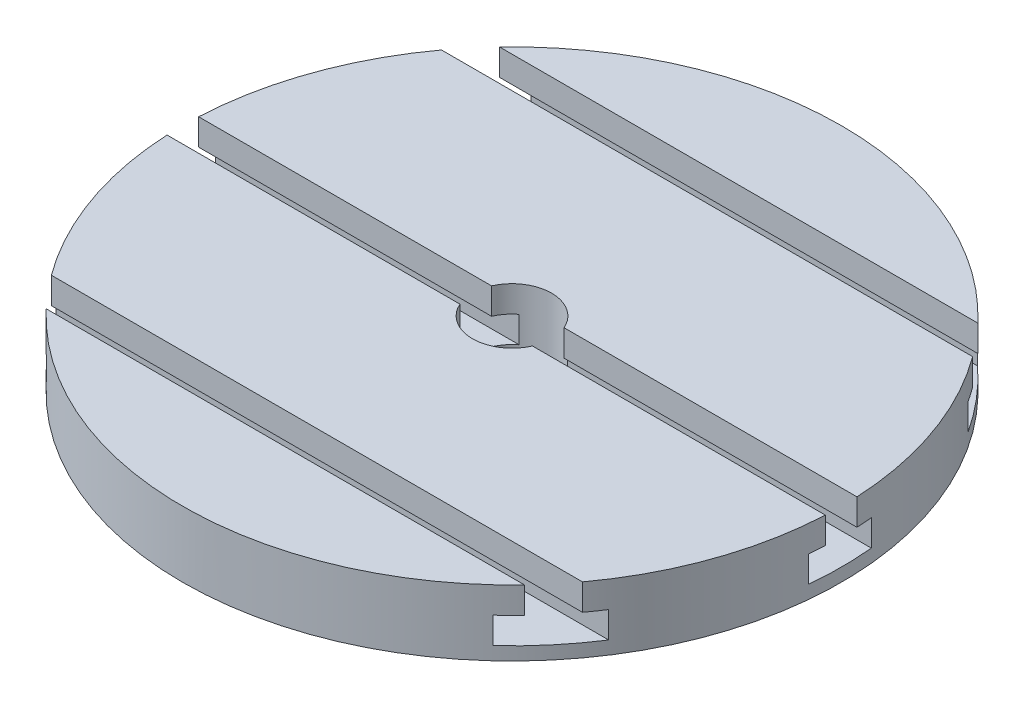
SolidWorks part; units mm, degrees
ref_plane "Спереди" through (0, 0, 0) normal (0, 0, 1) x (1, 0, 0)
ref_plane "Сверху" through (0, 0, 0) normal (0, 1, 0) x (1, 0, 0)
ref_plane "Справа" through (0, 0, 0) normal (1, 0, 0) x (0, 0, -1)
sketch "Эскиз1" plane through (0, 0, 0) normal (1, 0, 0) x (0, 0, -1)
  line L0 (0, -12.6281) -> (0, 29.9138) construction
  line L1 (15, 0) -> (125, 0)
  line L2 (15, 0) -> (15, 25)
  line L3 (15, 25) -> (125, 25)
  line L4 (125, 0) -> (125, 25)
revolve "Повернуть1" add sketch "Эскиз1" angle 360 about L0
sketch "Эскиз2" plane through (0, 0, 0) normal (1, 0, 0) x (0, 0, -1)
  line L1 (11.8734, 5) -> (11.8734, 15)
  line L2 (11.8734, 15) -> (6, 15)
  line L3 (6, 15) -> (6, 25)
  line L4 (125, 25) -> (-125, 25) construction
  line L5 (6, 25) -> (-6, 25)
  line L6 (15, 25) -> (-15, 25) construction
  line L10 (0, 28.7888) -> (0, -3.461) construction
  line L11 (-6, 15) -> (-6, 25)
  line L12 (-11.8734, 15) -> (-6, 15)
  line L13 (-11.8734, 5) -> (-11.8734, 15)
  line L14 (-11.8734, 5) -> (11.8734, 5)
  line L15 (68.1266, 5) -> (91.8734, 5)
  line L16 (91.8734, 5) -> (91.8734, 15)
  line L17 (91.8734, 15) -> (86, 15)
  line L18 (86, 15) -> (86, 25)
  line L19 (86, 25) -> (74, 25)
  line L20 (74, 15) -> (74, 25)
  line L21 (68.1266, 15) -> (74, 15)
  line L22 (68.1266, 5) -> (68.1266, 15)
  line L24 (-91.8734, 5) -> (-68.1266, 5)
  line L25 (-68.1266, 5) -> (-68.1266, 15)
  line L26 (-68.1266, 15) -> (-74, 15)
  line L27 (-74, 15) -> (-74, 25)
  line L28 (-74, 25) -> (-86, 25)
  line L29 (-86, 15) -> (-86, 25)
  line L30 (-91.8734, 15) -> (-86, 15)
  line L31 (-91.8734, 5) -> (-91.8734, 15)
  line L33 (-79.8734, 5) -> (-91.8734, 5) [skipped]
  line L34 (-80.1266, 5) -> (-68.1266, 5) [skipped]
  point P12 (0, 25)
  point P26 (80, 25)
  point P37 (-80, 25)
  dimension "D1" = 6
  dimension "D3" = 10
  dimension "D4" = 10
  dimension "D5" = 2
  dimension "D6" = 2
extrude "Вырез-Вытянуть1" cut sketch "Эскиз2" against normal mid plane 300
